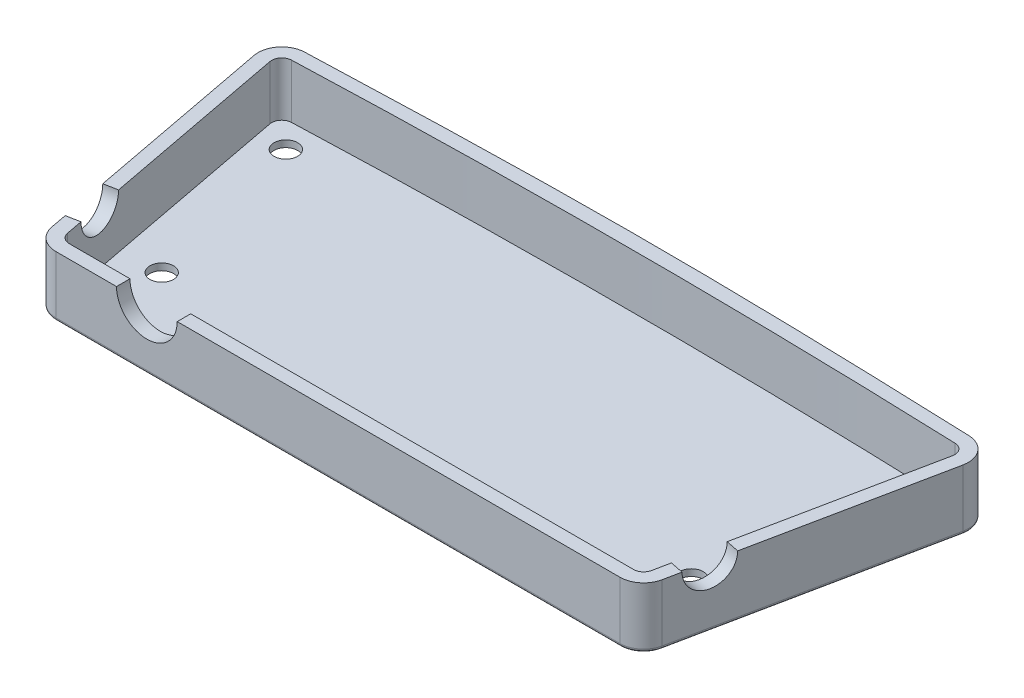
SolidWorks part; units mm, degrees
ref_plane "Front Plane" through (0, 0, 0) normal (0, 0, 1) x (1, 0, 0)
ref_plane "Top Plane" through (0, 0, 0) normal (0, 1, 0) x (1, 0, 0)
ref_plane "Right Plane" through (0, 0, 0) normal (1, 0, 0) x (0, 0, -1)
sketch "Sketch1" plane through (0, 0, 0) normal (0, 1, 0) x (1, 0, 0)
  line L0 (96.7105, 2.0926) -> (89.1406, -34.9403)
  line L6 (-6.4383, 1.7411) -> (0.6, -35.2933)
  line L7 (4.0385, -38.1399) -> (87.6709, -38.1399)
  line L8 (98.6699, 1.6921) -> (91.1, -35.3408)
  line L9 (4.0385, -36.1399) -> (87.6709, -36.1399)
  line L10 (-4.4735, 2.1145) -> (2.5649, -34.9199)
  line L11 (14.95, -35.3899) -> (73.95, -35.3899) construction
  circle A0 centre (0, 0) radius 1.75
  arc A5 (-6.4383, 1.7411) -> (-3.1315, 5.8921) centre (-2.9998, 2.3945) cw
  arc A6 (98.6699, 1.6921) -> (95.3726, 5.8905) centre (95.2409, 2.393) ccw
  arc A7 (87.6709, -38.1399) -> (91.1, -35.3408) centre (87.6709, -34.6399) ccw
  arc A8 (4.0385, -38.1399) -> (0.6, -35.2933) centre (4.0385, -34.6399) cw
  arc A9 (96.7105, 2.0926) -> (95.2973, 3.8919) centre (95.2409, 2.393) ccw
  arc A10 (87.6709, -36.1399) -> (89.1406, -34.9403) centre (87.6709, -34.6399) ccw
  arc A11 (4.0385, -36.1399) -> (2.5649, -34.9199) centre (4.0385, -34.6399) cw
  arc A12 (-4.4735, 2.1145) -> (-3.0563, 3.8935) centre (-2.9998, 2.3945) cw
  arc A13 (-3.0563, 3.8935) -> (95.2973, 3.8919) centre (46.1, -1302.5628) cw
  circle A14 centre (92.2, 0) radius 1.75
  circle A15 centre (6.6, -25) radius 1.75
  circle A16 centre (85.1, -24.9999) radius 1.75
  spline S1 degree 2 poles (-23.9, 5.0501) (46.1, 8.0501) (116.1, 5.0501) knots 0 0 0 1 1 1 weights 1 1.857143 1 construction
  spline S2 degree 2 poles (-23.9, 5.0501) (46.1, 8.0501) (116.1, 5.0501) knots 0 0 0 1 1 1 weights 1 1.857143 1
  dimension "D1" = 3.5
  dimension "D5" = 3.5
  dimension "D6" = 3.5
  dimension "D7" = 3.5
  dimension "D3" = 6
  dimension "D2" = 6
  dimension "D4" = 2.75
  dimension "D9" = 6
  dimension "D10" = 6
  dimension "D8" = 2
extrude "Boss-Extrude1" add sketch "Sketch1" along normal blind 1 contours S2 A5 L6 A8 L7 A7 L8 A6 A12 A13 A9 L0 A10 L9 A11 L10 | A13 A12 L10 A11 L9 A10 L0 A9 A14 A0 region at (45.9954, 0, 15.2806) region at (-4.8417, 0, -3.8618)
extrude "Boss-Extrude2" add sketch "Sketch1<5>" along normal blind 9 contours S2 A5 L6 A8 L7 A7 L8 A6 A12 A13 A9 L0 A10 L9 A11 L10 region at (-4.8417, 0, -3.8618)
sketch "Sketch1<5>" plane through (0, 0, 0) normal (0, 1, 0) x (1, 0, 0) same geometry as "Sketch1"
sketch "Sketch2" plane through (94.3805, 0, 19.2924) normal (0.9797, 0, 0.2003) x (0.2003, 0, -0.9797)
  line L0 (21.4184, 9) -> (-16.3803, 9) construction
  line L1 (-6.8803, 9) -> (-13.8803, 9)
  arc A0 (-6.8803, 9) -> (-13.8803, 9) centre (-10.3803, 9) cw
  dimension "D1" = 3.5
  dimension "D2" = 6
extrude "Cut-Extrude2" cut sketch "Sketch2" against normal blind 2
sketch "Sketch3" plane through (0, 0, 38.1399) normal (0, 0, 1) x (1, 0, 0)
  line L0 (4.0385, 9) -> (87.6709, 9) construction
  line L1 (22.0385, 9) -> (13.0385, 9)
  arc A0 (22.0385, 9) -> (13.0385, 9) centre (17.5385, 9) cw
  dimension "D1" = 4.5
  dimension "D2" = 13.5
extrude "Cut-Extrude3" cut sketch "Sketch3" against normal blind 7
fillet "Fillet1" radius 0.5 8 edges at (45.8547, 0, 38.1399) (89.8842, 0, 37.3512) (94.885, 0, 16.8244) (97.9934, 0, -4.5548) (-5.7374, 0, -4.5753) (-2.9191, 0, 16.7761) (1.8066, 0, 37.3359)
sketch "Sketch4" plane through (-5.8945, 0, 1.1202) normal (-0.9824, 0, 0.1867) x (0.1867, 0, 0.9824)
  line L0 (-2.9125, 9) -> (34.7848, 9) construction
  line L1 (25.2848, 9) -> (32.2848, 9)
  arc A0 (32.2848, 9) -> (25.2848, 9) centre (28.7848, 9) cw
  point P3 (0, 0)
  dimension "D1" = 3.5
  dimension "D2" = 6
extrude "Cut-Extrude4" cut sketch "Sketch4" against normal blind 2
